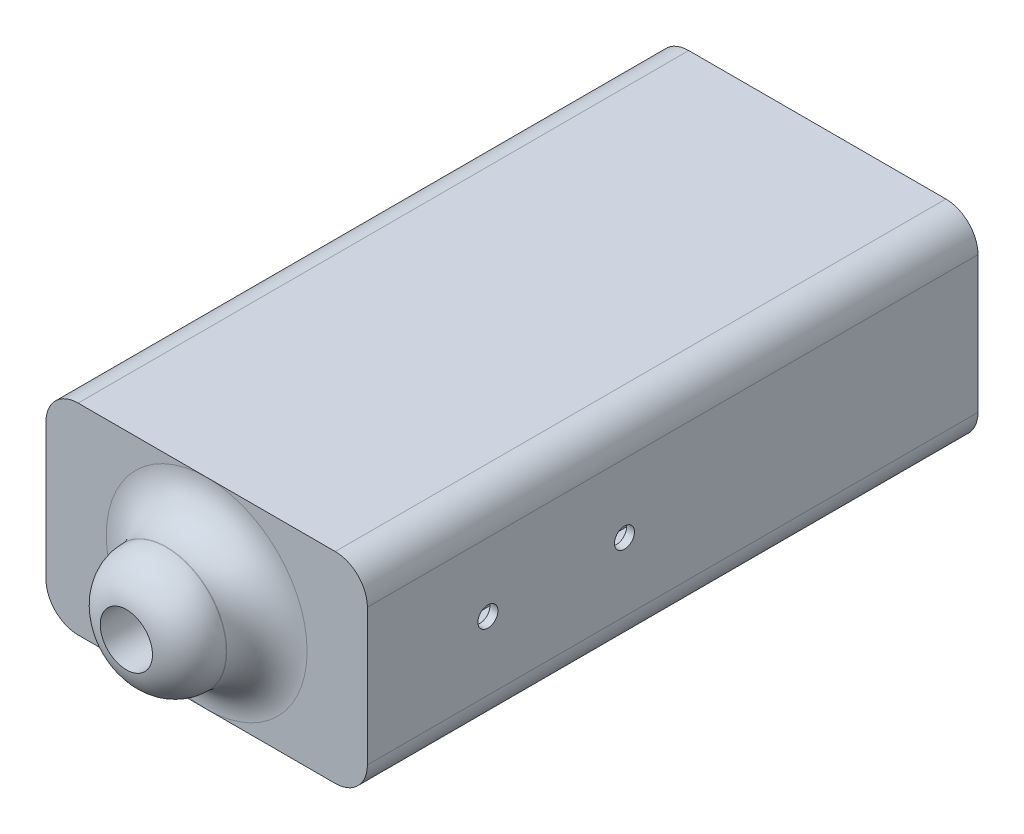
SolidWorks part; units mm, degrees
material "PLA Aero Bambu"
ref_plane "Front Plane" through (0, 0, 0) normal (0, 0, 1) x (1, 0, 0)
ref_plane "Top Plane" through (0, 0, 0) normal (0, 1, 0) x (1, 0, 0)
ref_plane "Right Plane" through (0, 0, 0) normal (1, 0, 0) x (0, 0, -1)
sketch "Sketch1" plane through (0, 0, 0) normal (0, 0, 1) x (1, 0, 0)
  line L1 (-20, 12.5) -> (20, 12.5)
  line L2 (-20, 12.5) -> (-20, -12.5)
  line L3 (-20, -12.5) -> (20, -12.5)
  line L4 (20, 12.5) -> (20, -12.5)
  line L5 (-20, 12.5) -> (20, -12.5) construction
  line L6 (-20, -12.5) -> (20, 12.5) construction
  circle A0 centre (0, 0) radius 2
  point P0 (0, 0)
  dimension "D3" = 4
  dimension "D1" = 25
  dimension "D2" = 40
extrude "Boss-Extrude1" add sketch "Sketch1" against normal blind 1
sketch "Sketch2" plane through (0, 0, -1) normal (0, 0, -1) x (-1, 0, 0)
  line L0 (-20, 12.5) -> (-20, -12.5)
  line L1 (20, -12.5) -> (-20, -12.5) construction
  line L2 (-20, -12.5) -> (20, -12.5)
  line L3 (20, -12.5) -> (20, 12.5)
  line L4 (20, 12.5) -> (-20, 12.5)
  line L5 (19, 11.5) -> (-19, 11.5)
  line L6 (-19, 11.5) -> (-19, -11.5)
  line L7 (-19, -11.5) -> (19, -11.5)
  line L8 (19, -11.5) -> (19, 11.5)
  dimension "D1" = 1
extrude "Boss-Extrude2" add sketch "Sketch2" along normal blind 75
fillet "Fillet2" radius 4 8 edges at (20, 12.5, -38) (20, -12.5, -38) (-20, -12.5, -38) (-20, 12.5, -38) (-19, -11.5, -38.5) (-19, 11.5, -38.5) (19, 11.5, -38.5) (19, -11.5, -38.5)
sketch "Sketch4" plane through (0, 0, 0) normal (0, 0, 1) x (1, 0, 0)
  circle A0 centre (0, 0) radius 7.5
  circle A1 centre (0, 0) radius 3.25
  dimension "D1" = 6.5
  dimension "D2" = 15
extrude "Boss-Extrude3" add sketch "Sketch4" along normal blind 10
fillet "Fillet3" radius 5 2 edges at (7.5, 0, 0) (7.5, 0, 10)
sketch "Sketch5" plane through (20, 0, 0) normal (1, 0, 0) x (0, 0, -1)
  circle A0 centre (15, 0) radius 1.25
  circle A1 centre (32, 0) radius 1.25
  point P5 (30.5, 0)
  point P6 (0, 0)
  dimension "D1" = 2.5
  dimension "D3" = 2.5
  dimension "D2" = 15
  dimension "D4" = 17
extrude "Cut-Extrude1" cut sketch "Sketch5" against normal through all
sketch "Sketch10" plane through (0, -11.5, 0) normal (0, 1, 0) x (1, 0, 0)
  line L0 (-20, 32.5) -> (20, 32.5)
  line L1 (15, 1) -> (-15, 1) construction
  line L2 (20, 30.75) -> (20, 33.25) construction
  line L3 (-15, 76) -> (-15, 1) construction
  line L5 (-20, 33.25) -> (-20, 30.75) construction
  line L6 (-15, 47.6018) -> (7.4768, 47.6018)
  line L7 (-15, 47.6018) -> (-15, 25.1)
  line L8 (-15, 25.1) -> (7.4768, 25.1)
  line L9 (7.4768, 47.6018) -> (7.4768, 25.1)
  point P2 (13.2446, 32.5)
  line B0 (7.4768, 39.9) -> (13.2446, 39.9) construction
  line B1 (-15, 47.6018) -> (7.4768, 47.6018) construction
  line B2 (-15, 47.6018) -> (-15, 25.1) construction
  line B3 (-15, 25.1) -> (7.4768, 25.1) construction
  line B4 (7.4768, 47.6018) -> (7.4768, 25.1) construction
  line B5 (13.2446, 39.9) -> (13.2446, 25.1) construction
  line B6 (13.2446, 25.1) -> (7.4768, 25.1) construction
  line B7 (3.3268, 47.6165) -> (3.3268, 52.475) construction
  line B8 (3.3268, 52.475) -> (5.8268, 52.475) construction
  line B9 (5.8268, 52.475) -> (5.7933, 47.65) construction
  line B10 (5.8268, 25.1) -> (5.8268, 20.2604) construction
  line B11 (5.8268, 20.2604) -> (3.3268, 20.275) construction
  line B12 (3.3268, 20.275) -> (3.3268, 25.1335) construction
  line M3 (-15, 76) -> (-15, 1)
  dimension "D1" = 31.5
sketch_block_instance "Block1-1"
sketch_block "Block1"
extrude "Boss-Extrude4" add sketch "Sketch10" along normal blind 6 contours L9 L0 L8 M3 | L9 L6 L0 M3 region at (-3.7616, -11.5, -40.0509) region at (-3.7616, -11.5, -28.8)
sketch "Sketch12" plane through (0, -11.5, 0) normal (0, 1, 0) x (1, 0, 0)
  line L0 (3.3268, 52.475) -> (5.8268, 52.475) construction
  line L1 (3.3268, 47.6165) -> (0.8268, 47.6165)
  line L2 (3.3268, 47.6165) -> (3.3268, 52.475)
  line L3 (3.3268, 52.475) -> (0.8268, 52.475)
  line L4 (0.8268, 47.6165) -> (0.8268, 52.475)
  line L6 (3.3268, 25.1335) -> (0.8268, 25.1335)
  line L7 (3.3268, 25.1335) -> (3.3268, 20.275)
  line L8 (3.3268, 20.275) -> (0.8268, 20.2896)
  line L9 (0.8268, 25.1335) -> (0.8268, 20.2896)
  line L11 (5.8268, 20.2604) -> (3.3268, 20.275) construction
  point P5 (2.0768, 52.475)
  dimension "D1" = 0
  dimension "D2" = 2.5
  dimension "D3" = 2.5
extrude "Boss-Extrude5" add sketch "Sketch12" along normal blind 15
sketch "Sketch13" plane through (3.3268, 0, 0) normal (1, 0, 0) x (0, 0, -1)
  line L0 (47.6018, -5.5) -> (25.1, -5.5) construction
  line L1 (20.275, 3.5) -> (25.1335, 3.5) construction
  line L2 (47.6165, 3.5) -> (52.475, 3.5) construction
  circle A0 centre (22.7042, 0) radius 1.35
  circle A1 centre (50.0458, 0) radius 1.35
  point P6 (0, 0)
  point P7 (50.0458, 3.5)
  point P11 (22.7042, 3.5)
  dimension "D2" = 2.7
  dimension "D3" = 2.7
  dimension "D1" = 5.5
extrude "Cut-Extrude3" cut sketch "Sketch13" against normal blind 12
sketch "Sketch15" plane through (0, -11.5, 0) normal (0, 1, 0) x (1, 0, 0)
  line L0 (19, 76) -> (19, 1) construction
  line L1 (9, 18) -> (14, 18)
  line L2 (9, 18) -> (9, 12)
  line L3 (9, 12) -> (14, 12)
  line L4 (14, 18) -> (14, 12)
  line L5 (9, 12) -> (14, 18) construction
  line L6 (14, 12) -> (9, 18) construction
  line L8 (15, 1) -> (-15, 1) construction
  point P6 (11.5, 15)
  point P7 (0, 0)
  point P8 (0, 0)
  dimension "D1" = 5
  dimension "D2" = 6
  dimension "D3" = 5
  dimension "D4" = 14
extrude "Boss-Extrude6" add sketch "Sketch15" along normal blind 14
sketch "Sketch16" plane through (14, 0, 0) normal (1, 0, 0) x (0, 0, -1)
  circle A0 centre (15, 0) radius 1.25
extrude "Cut-Extrude4" cut sketch "Sketch16" against normal blind 5
